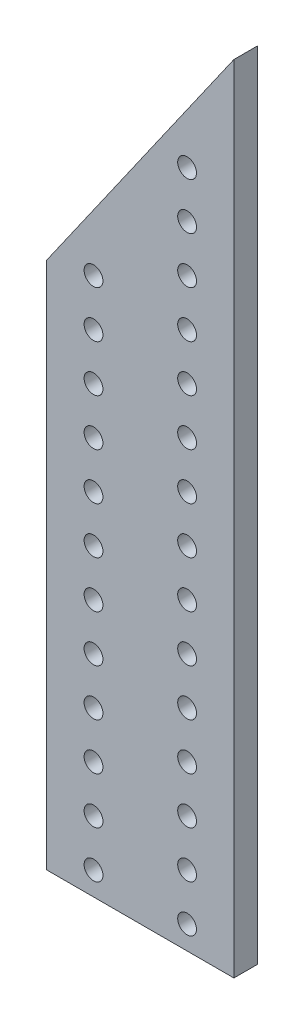
SolidWorks part; units mm, degrees
material "6061-T6 (SS)"
ref_plane "Front Plane" through (0, 0, 0) normal (0, 0, 1) x (1, 0, 0)
ref_plane "Top Plane" through (0, 0, 0) normal (0, 1, 0) x (1, 0, 0)
ref_plane "Right Plane" through (0, 0, 0) normal (1, 0, 0) x (0, 0, -1)
sketch "Sketch1" plane through (0, 0, 0) normal (0, 0, 1) x (1, 0, 0)
  line L1 (0, 0) -> (50.8, 0)
  line L2 (0, 0) -> (0, 215.9)
  line L3 (0, 215.9) -> (50.8, 215.9)
  line L4 (50.8, 0) -> (50.8, 215.9)
  dimension "D1" = 50.8
  dimension "D2" = 215.9
extrude "Boss-Extrude1" add sketch "Sketch1" along normal blind 6.35
sketch "Sketch2" plane through (0, 0, 0) normal (0, 0, -1) x (-1, 0, 0)
  line L0 (-50.8, 0) -> (-50.8, 215.9) construction
  line L1 (0, 0) -> (-50.8, 0) construction
  circle A0 centre (-38.1, 6.35) radius 2.5527
  circle A1 centre (-12.7, 6.35) radius 2.5527
  circle A2 centre (-38.1, 19.05) radius 2.5527
  circle A3 centre (-12.7, 19.05) radius 2.5527
  circle A4 centre (-38.1, 31.75) radius 2.5527
  circle A5 centre (-12.7, 31.75) radius 2.5527
  circle A6 centre (-38.1, 44.45) radius 2.5527
  circle A7 centre (-12.7, 44.45) radius 2.5527
  circle A8 centre (-38.1, 57.15) radius 2.5527
  circle A9 centre (-12.7, 57.15) radius 2.5527
  circle A10 centre (-38.1, 69.85) radius 2.5527
  circle A11 centre (-12.7, 69.85) radius 2.5527
  circle A12 centre (-38.1, 82.55) radius 2.5527
  circle A13 centre (-12.7, 82.55) radius 2.5527
  circle A14 centre (-38.1, 95.25) radius 2.5527
  circle A15 centre (-12.7, 95.25) radius 2.5527
  circle A16 centre (-38.1, 107.95) radius 2.5527
  circle A17 centre (-12.7, 107.95) radius 2.5527
  circle A18 centre (-38.1, 120.65) radius 2.5527
  circle A19 centre (-12.7, 120.65) radius 2.5527
  circle A20 centre (-38.1, 133.35) radius 2.5527
  circle A21 centre (-12.7, 133.35) radius 2.5527
  circle A22 centre (-38.1, 146.05) radius 2.5527
  circle A23 centre (-12.7, 146.05) radius 2.5527
  circle A24 centre (-38.1, 158.75) radius 2.5527
  circle A25 centre (-12.7, 158.75) radius 2.5527 construction
  circle A26 centre (-38.1, 171.45) radius 2.5527
  circle A27 centre (-12.7, 171.45) radius 2.5527
  circle A32 centre (-38.1, 184.15) radius 2.5527
  dimension "D1" = 25.4
  dimension "D2" = 12.7
  dimension "D3" = 5.1054
  dimension "D4" = 5.1054
  dimension "D5" = 6.35
  dimension "D6" = 6.35
  dimension "D8" = 12.7
  dimension "D9" = 12.7
  dimension "D10" = 5.1054
  dimension "D11" = 12.7
  dimension "D7" = 14
extrude "Cut-Extrude1" cut sketch "Sketch2" against normal through all
sketch "Sketch3" plane through (0, 0, 0) normal (0, 0, -1) x (-1, 0, 0)
  line L0 (-50.8, 215.9) -> (0, 143.3501)
  line L1 (-50.8, 215.9) -> (0, 215.9) construction
  line L3 (0, 215.9) -> (0, 0) construction
  line L4 (0, 143.3501) -> (0, 215.9)
  line L5 (0, 215.9) -> (-50.8, 215.9)
  dimension "D1" = 55
  dimension "D2" = 50.8
extrude "Cut-Extrude2" cut sketch "Sketch3" against normal through all
